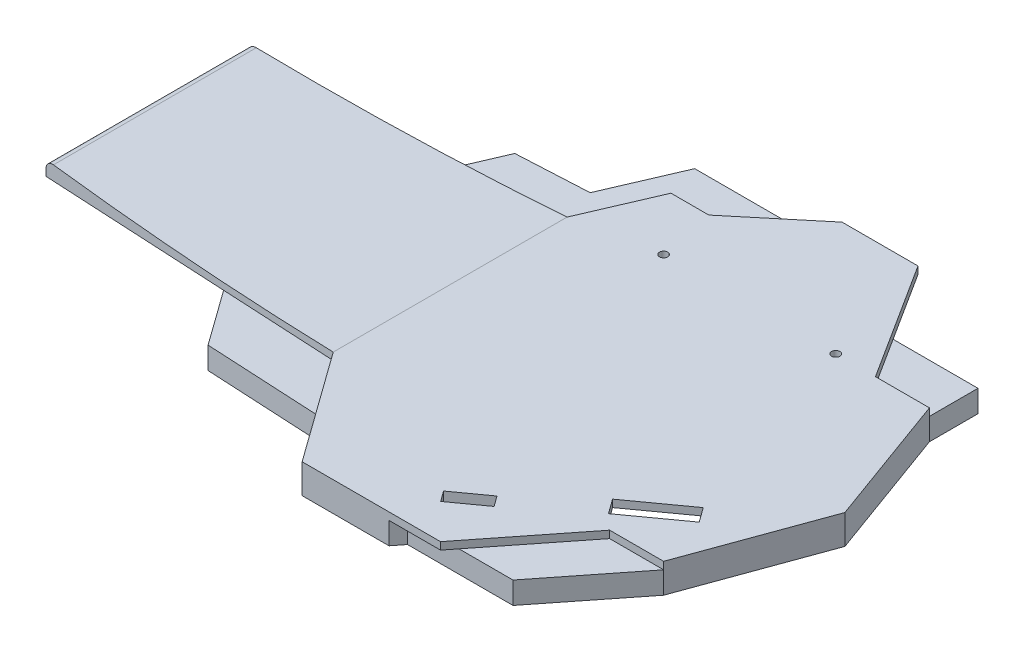
SolidWorks part; units mm, degrees
ref_plane "前视基准面" through (0, 0, 0) normal (0, 0, 1) x (1, 0, 0)
ref_plane "上视基准面" through (0, 0, 0) normal (0, 1, 0) x (1, 0, 0)
ref_plane "右视基准面" through (0, 0, 0) normal (1, 0, 0) x (0, 0, -1)
other "Configuration Table"
sketch "草图2" plane through (0, 0, 0) normal (0, 1, 0) x (1, 0, 0)
  line L0 (0, 0) -> (243.6421, 0) construction
  line L30 (176.8295, 36.1855) -> (82.5273, -31.8251) construction
  line L35 (141.8216, 68.0827) -> (121.1619, 68.0827)
  line L36 (176.8295, 36.1855) -> (190, 0)
  line L37 (104.1466, -61.9173) -> (82.5273, -31.8251)
  line L38 (82.5273, -31.8251) -> (0, -27.5)
  line L39 (0, -27.5) -> (0, 27.5)
  line L40 (0, 27.5) -> (82.5273, 31.8251)
  line L43 (190, 0) -> (176.8295, -36.1855)
  line L45 (82.5273, 31.8251) -> (91.0398, 51.6089)
  line L51 (104.1466, -61.9173) -> (190, 0) construction
  line L53 (141.8216, -61.9173) -> (104.1466, -61.9173)
  line L55 (82.5273, 31.8251) -> (342.4089, 31.8251) construction
  line L57 (176.8295, 36.1855) -> (176.8295, 0) construction
  line L58 (176.8295, 0) -> (176.8295, -36.1855) construction
  line L59 (82.5273, -31.8251) -> (342.4089, -31.8251) construction
  line L62 (91.0398, 51.6089) -> (101.351, 51.6089)
  line L63 (101.351, 51.6089) -> (121.1619, 68.0827)
  line L64 (141.8216, 68.0827) -> (162.1337, 36.1855)
  line L65 (162.1337, 36.1855) -> (176.8295, 36.1855)
  line L66 (176.8295, -36.1855) -> (162.1337, -36.1855)
  line L67 (162.1337, -36.1855) -> (141.8216, -61.9173)
  dimension "D1" = 190
  dimension "D2" = 130
  dimension "D4" = 55
  dimension "D6" = 93
  dimension "D7" = 93
  dimension "D8" = 140
extrude "凸台-拉伸1" add sketch "草图2" along normal blind 2
sketch "草图6" plane through (0, 2, 0) normal (0, 1, 0) x (1, 0, 0)
  line L0 (82.5273, 31.8251) -> (82.5273, -31.8251)
  line L1 (82.5273, -31.8251) -> (0, -27.5)
  line L2 (0, -27.5) -> (0, 27.5)
  line L3 (0, 27.5) -> (82.5273, 31.8251)
extrude "凸台-拉伸2" add sketch "草图6" along normal blind 2
sketch "草图7" plane through (0, 0, 0) normal (0, 0, 1) x (1, 0, 0)
  line L2 (82.5273, 2) -> (82.5273, 30.7408)
  line L3 (82.5273, 30.7408) -> (0, 4)
  spline S0 degree 2 poles (82.5273, 2) (41.2153, 1.0012) (0, 4) knots 0 0 0 1 1 1
extrude "切除-拉伸3" cut sketch "草图7" against normal through all both and the other way through all
fillet "圆角1" radius 2 1 edges at (0, 4, 0)
ref_plane "基准面3" through (0, -12, 0) normal (0, -1, 0) x (-1, 0, 0)
sketch "草图10" plane through (0, 0, 0) normal (0, -1, 0) x (1, 0, 0)
  line L0 (0, 27.5) -> (82.5273, 31.8251)
  line L1 (82.5273, 31.8251) -> (171.8529, 31.8251)
  line L2 (171.8529, 31.8251) -> (171.8529, -31.8251)
  line L3 (171.8529, -31.8251) -> (82.5273, -31.8251)
  line L4 (82.5273, -31.8251) -> (0, -27.5)
  line L5 (0, -27.5) -> (0, 27.5)
sketch "草图12" plane through (0, 2, 0) normal (0, 1, 0) x (1, 0, 0)
  line L0 (176.8295, 36.1855) -> (82.5273, -31.8251)
  line L1 (190, 0) -> (104.1466, -61.9173)
  line L2 (183.4148, 18.0928) -> (93.337, -46.8712) construction
  line L3 (190, 0) -> (176.8295, 36.1855) construction
  line L4 (82.5273, -31.8251) -> (104.1466, -61.9173) construction
sketch "草图13" plane through (0, 0, 0) normal (0, -1, 0) x (1, 0, 0)
  line L0 (53.5015, -30.3039) -> (58.4123, -41.717)
  line L1 (82.5273, -31.8251) -> (0, -27.5) construction
  line L2 (58.4123, -41.717) -> (77.9269, -42.7397)
  line L3 (77.9269, -42.7397) -> (86.4844, -62.6282)
  line L4 (86.4844, -62.6282) -> (136.1647, -62.6282)
  line L5 (176.8295, 36.1855) -> (190, 0)
  line L6 (190, 0) -> (176.8295, -36.1855)
  line L7 (136.1647, -62.6282) -> (144.5841, -49.4069)
  line L8 (144.5841, -49.4069) -> (176.8295, -49.4069)
  line L9 (176.8295, -49.4069) -> (176.8295, -36.1855)
  line L11 (176.8295, 36.1855) -> (158.7432, 59.0976)
  line L12 (158.7432, 59.0976) -> (130.0164, 59.0976)
  line L13 (130.0164, 59.0976) -> (127.7906, 61.9173)
  line L14 (104.1466, 61.9173) -> (141.8216, 61.9173) construction
  line L15 (127.7906, 61.9173) -> (104.1466, 61.9173)
  line L16 (104.1466, 61.9173) -> (93.337, 46.8712)
  line L17 (93.337, 46.8712) -> (61.8459, 45.2208)
  line L18 (61.8459, 45.2208) -> (51.0363, 30.1747)
  line L19 (0, 27.5) -> (82.5273, 31.8251) construction
  line L20 (51.0363, 30.1747) -> (171.8529, 31.8251)
  line L21 (171.8529, 31.8251) -> (171.8529, -31.8251)
  line L22 (171.8529, -31.8251) -> (53.5015, -30.3039)
extrude "凸台-拉伸4" add sketch "草图13" along normal blind 6 contours L18 L20 L21 L22 L0 L2 L3 L4 L7 L8 L9 L6 L5 L11 L12 L13 L15 L16 L17
sketch "草图15" plane through (0, 2, 0) normal (0, 1, 0) x (1, 0, 0)
  circle A0 centre (151.351, 36.16) radius 1.1
  circle A1 centre (104.4979, 36.16) radius 1.06
  point P0 (151.351, 36.16)
  point P3 (104.4979, 36.16)
hole_wizard "#4-40 螺纹孔2" positions "草图15" profile "草图16" tap size "#4-40" standard "ANSI Inch" end condition through all
sketch "草图16" plane through (151.351, 2, -36.16) normal (1, 0, 0) x (0, 0, 1)
  line L0 (0, 0) -> (0, 8)
  line L1 (0, 8) -> (1.1303, 8)
  line L2 (1.1303, 8) -> (1.1303, 0)
  line L5 (1.1303, 0) -> (0, 0)
  line L11 (0, -6.35) -> (0, 107.95) construction
  dimension "通孔螺纹孔钻头直径" = 2.2606
  dimension "通孔螺纹孔钻头深度" = 8
cosmetic thread "孔螺纹线2" parameters "D2"=2.8448
cosmetic thread "孔螺纹线3" parameters "D2"=2.8448
sketch "草图17" plane through (0, 2, 0) normal (0, 1, 0) x (1, 0, 0)
  line L1 (127.9245, 6.0352) -> (127.9245, 66.2872) construction
  line L2 (127.9245, 71.5706) -> (127.9245, 3.7208) construction
  line L3 (116.0112, 26.5953) -> (142.1812, 26.5953)
  arc A1 (116.0112, 26.5953) -> (142.1812, 26.5953) centre (129.0962, 34.7996) ccw
sketch "草图18" plane through (0, 2, 0) normal (0, 1, 0) x (1, 0, 0)
  line L4 (169.5639, -18.1259) -> (155.2183, -28.4719)
  line L5 (172.4314, -22.1019) -> (169.5639, -18.1259)
  line L6 (158.0858, -32.4479) -> (172.4314, -22.1019)
  line L7 (155.2183, -28.4719) -> (158.0858, -32.4479)
  line L8 (169.5639, -18.1259) -> (155.2183, -28.4719)
  line L9 (172.4314, -22.1019) -> (169.5639, -18.1259)
  line L10 (158.0858, -32.4479) -> (172.4314, -22.1019)
  line L11 (155.2183, -28.4719) -> (158.0858, -32.4479)
  line L12 (130.3021, -49.5646) -> (132.3616, -52.4203)
  line L13 (132.3616, -52.4203) -> (140.8147, -46.3239)
  line L14 (140.8147, -46.3239) -> (138.7552, -43.4683)
  line L15 (138.7552, -43.4683) -> (130.3021, -49.5646)
  line L16 (130.3021, -49.5646) -> (132.3616, -52.4203)
  line L17 (132.3616, -52.4203) -> (140.8147, -46.3239)
  line L18 (140.8147, -46.3239) -> (138.7552, -43.4683)
  line L19 (138.7552, -43.4683) -> (130.3021, -49.5646)
  dimension "D1" = 0
  dimension "D2" = 0
extrude "切除-拉伸7" cut sketch "草图18" against normal through all
